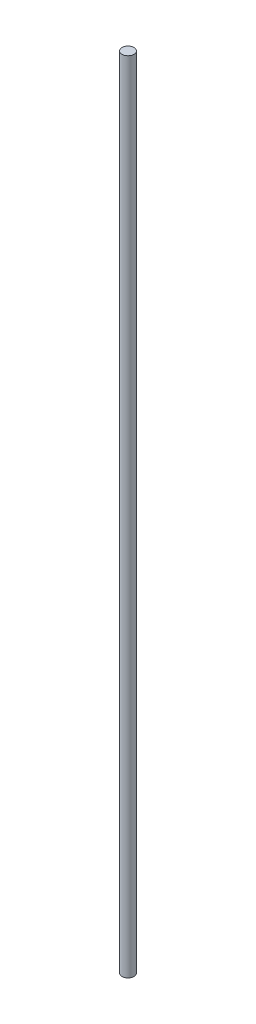
SolidWorks part; units mm, degrees
ref_plane "Plan de face" through (0, 0, 0) normal (0, 0, 1) x (1, 0, 0)
ref_plane "Plan de dessus" through (0, 0, 0) normal (0, 1, 0) x (1, 0, 0)
ref_plane "Plan de droite" through (0, 0, 0) normal (1, 0, 0) x (0, 0, -1)
sketch "Esquisse1" plane through (0, 0, 0) normal (0, 1, 0) x (1, 0, 0)
  circle A0 centre (0, 0) radius 2.5
  dimension "D1" = 5
extrude "Boss.-Extru.1" add sketch "Esquisse1" along normal up to surface (333.7 mm away)
